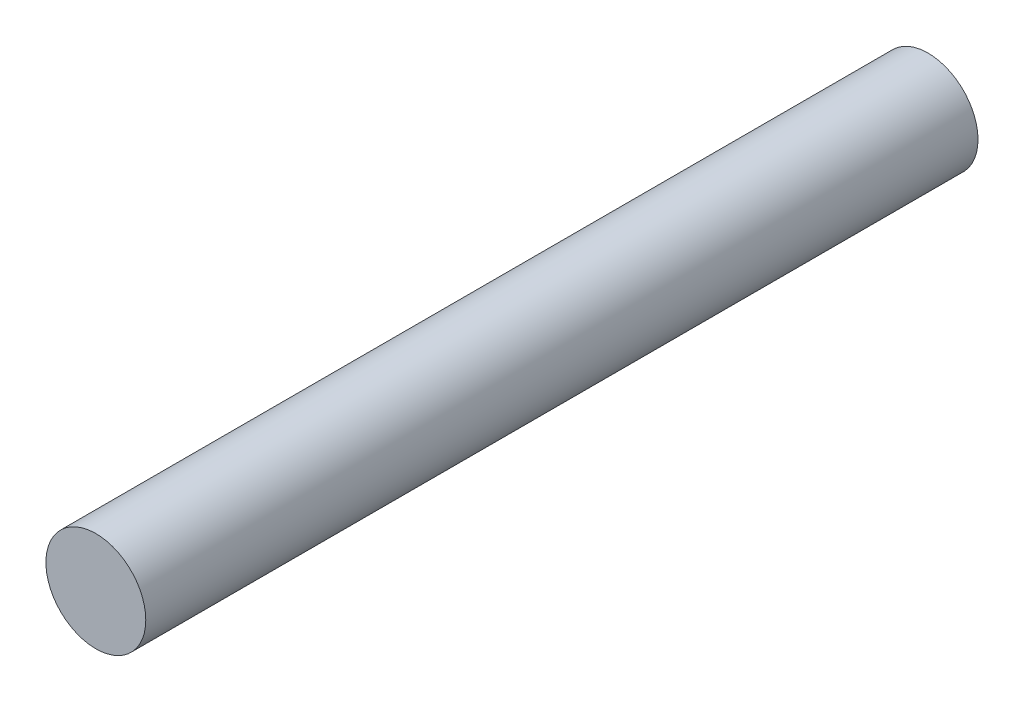
SolidWorks part; units mm, degrees
ref_plane "Front Plane" through (0, 0, 0) normal (0, 0, 1) x (1, 0, 0)
ref_plane "Top Plane" through (0, 0, 0) normal (0, 1, 0) x (1, 0, 0)
ref_plane "Right Plane" through (0, 0, 0) normal (1, 0, 0) x (0, 0, -1)
ref_axis "Axis1" through (0, 0, -2.5) along (0, 0, 1)
sketch "Sketch1" plane through (0, 0, 0) normal (0, 0, 1) x (1, 0, 0)
  circle A0 centre (0, 0) radius 3
  dimension "D1" = 6
extrude "Boss-Extrude1" add sketch "Sketch1" along normal blind 50
